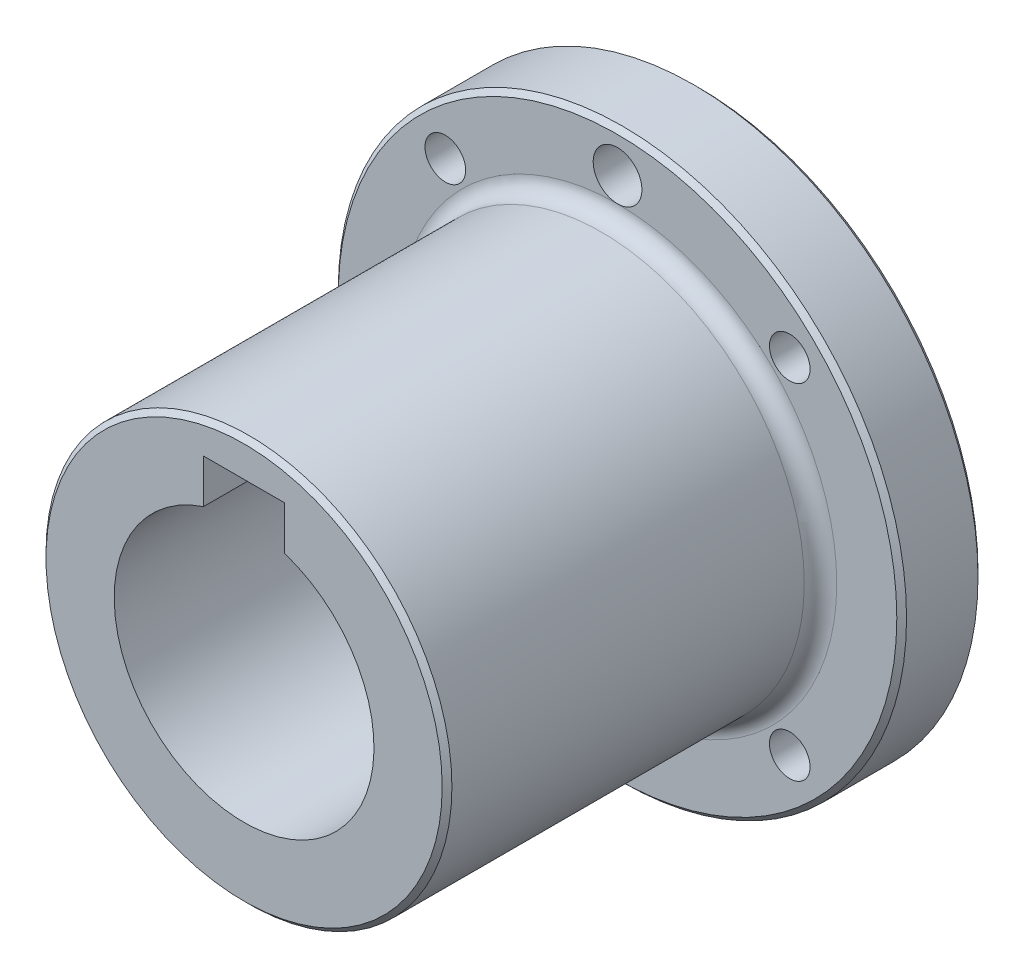
SolidWorks part; units mm, degrees
material "Plain Carbon Steel"
ref_plane "Front Plane" through (0, 0, 0) normal (0, 0, 1) x (1, 0, 0)
ref_plane "Top Plane" through (0, 0, 0) normal (0, 1, 0) x (1, 0, 0)
ref_plane "Right Plane" through (0, 0, 0) normal (1, 0, 0) x (0, 0, -1)
sketch "Sketch1" plane through (0, 0, 0) normal (0, 0, 1) x (1, 0, 0)
  circle A0 centre (100, 0) radius 17.5
  circle A2 centre (100, 0) radius 17.5 construction
extrude "Boss-Extrude1" add sketch "Sketch1" along normal blind 5
hole_wizard "Ø3.0mm Dowel Hole1" positions "Sketch4" profile "Sketch5" hole size "Ø3.0" standard "ANSI Metric" end condition through all
sketch "Sketch4" plane through (0, 0, 0) normal (0, 0, -1) x (-1, 0, 0)
  circle A0 centre (-100, 15) radius 2.5 construction
  point P0 (-100, 15)
sketch "Sketch5" plane through (100, 15, 0) normal (1, 0, 0) x (0, 1, 0)
  line L0 (0, 0) -> (0, 5)
  line L1 (0, 5) -> (1.5, 5)
  line L2 (1.5, 5) -> (1.5, 0)
  line L5 (1.5, 0) -> (0, 0)
  line L11 (0, -6.35) -> (0, 107.95) construction
  dimension "Thru Hole Dia." = 3
  dimension "Thru Hole Depth" = 5
hole_wizard "M3x0.5 Tapped Hole1" positions "Sketch8" profile "Sketch9" tap size "M3x0.5" standard "ANSI Metric" end condition through all
sketch "Sketch8" plane through (0, 0, 0) normal (0, 0, -1) x (-1, 0, 0)
  circle A0 centre (-110.6066, 10.6066) radius 1.6 construction
  circle A1 centre (-110.6066, -10.6066) radius 1.6 construction
  circle A2 centre (-89.3934, -10.6066) radius 1.6 construction
  circle A4 centre (-89.3934, 10.6066) radius 1.6 construction
  point P0 (-110.6066, 10.6066)
  point P3 (-89.3934, 10.6066)
  point P6 (-110.6066, -10.6066)
  point P9 (-89.3934, -10.6066)
sketch "Sketch9" plane through (110.6066, 10.6066, 0) normal (1, 0, 0) x (0, 1, 0)
  line L0 (0, 0) -> (0, 5)
  line L1 (0, 5) -> (1.25, 5)
  line L2 (1.25, 5) -> (1.25, 0)
  line L5 (1.25, 0) -> (0, 0)
  line L11 (0, -6.35) -> (0, 107.95) construction
  dimension "Thru Tap Drill Dia." = 2.5
  dimension "Thru Tap Drill Depth" = 5
cosmetic thread "Hole Thread1" parameters "D2"=3
cosmetic thread "Hole Thread2" parameters "D2"=3
cosmetic thread "Hole Thread3" parameters "D2"=3
cosmetic thread "Hole Thread4" parameters "D2"=3
sketch "Sketch10" plane through (0, 0, 5) normal (0, 0, 1) x (1, 0, 0)
  circle A0 centre (100, 0) radius 12.5
  dimension "D1" = 25
extrude "Boss-Extrude2" add sketch "Sketch10" along normal blind 23
chamfer "Chamfer1" distance 0.3 angle 45 8 edges at (98.5, 15, 0) (88.1434, -10.6066, 0) (109.3566, -10.6066, 0) (88.1434, 10.6066, 0) (109.3566, 10.6066, 0) (112.5, 0, 28) (117.5, 0, 5) (117.5, 0, 0)
sketch "KeySketch" plane through (101.369, 1.0806, 28) normal (0, 0, 1) x (1, 0, 0)
  line L0 (-1.369, -9.0806) -> (-1.369, 9.2194) construction
  line L1 (-9.369, -1.0806) -> (6.631, -1.0806) construction
  line L2 (-3.869, 6.5187) -> (-3.869, 9.2194)
  line L4 (1.131, 9.2194) -> (1.131, 6.5187)
  line L5 (1.131, 9.2194) -> (-3.869, 9.2194)
  arc A0 (-3.869, 6.5187) -> (1.131, 6.5187) centre (-1.369, -1.0806) ccw
  circle A1 centre (-1.369, -1.0806) radius 12.5 construction
  point P10 (-1.369, 9.2194)
  point P12 (-1.369, 13.9194)
  dimension "Diameter" = 16
  dimension "Width" = 5
  dimension "Depth" = 2.3
extrude "Keyway" cut sketch "KeySketch" against normal through all
other "bore with deep pattern keyway din 6886 p1<1>"
fillet "Fillet1" radius 1 1 edges at (112.5, 0, 5)
